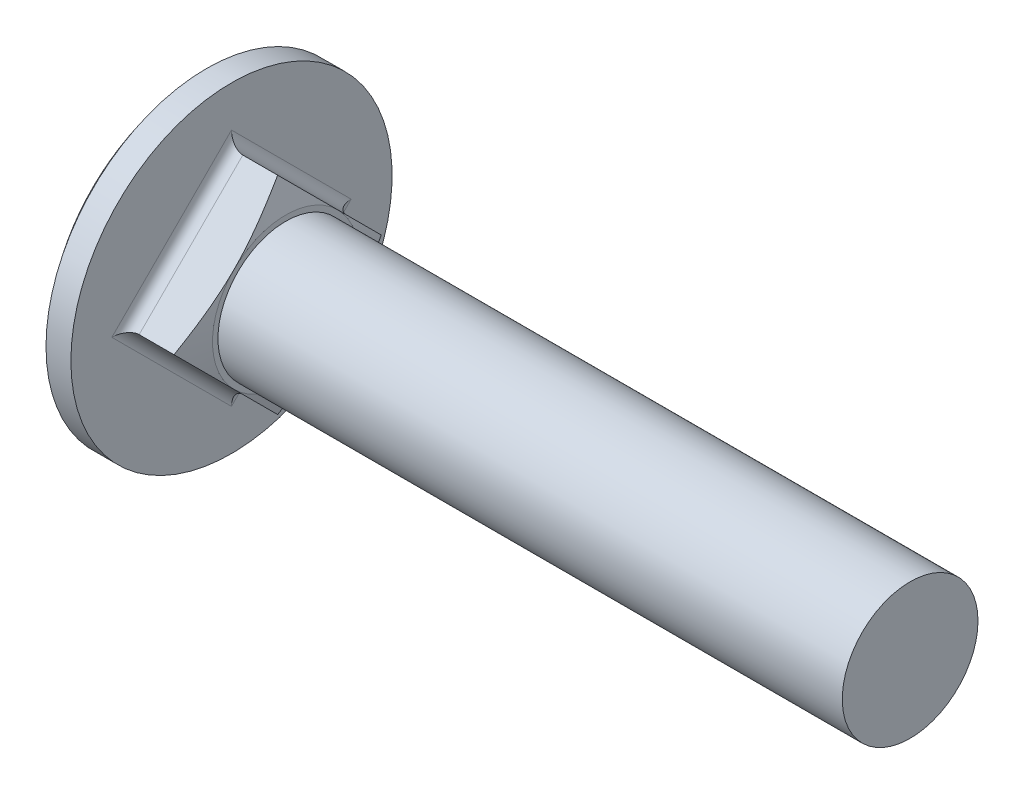
SolidWorks part; units mm, degrees
ref_plane "Front" through (0, 0, 0) normal (0, 0, 1) x (1, 0, 0)
ref_plane "Top" through (0, 0, 0) normal (0, 1, 0) x (1, 0, 0)
ref_plane "Right" through (0, 0, 0) normal (1, 0, 0) x (0, 0, -1)
sketch "Sketch2" plane through (0, 0, 0) normal (0, 0, 1) x (1, 0, 0)
  line L0 (-6.2668, 0) -> (14.9447, 0) construction
  line L1 (3.6, 0) -> (3.6, 7.1)
  line L3 (3.6, 7.1) -> (2.5, 7.1)
  line L4 (0, 0) -> (3.6, 0)
  arc A0 (2.5, 7.1) -> (0, 0) centre (11.332, 0) ccw
  dimension "k" = 3.6
  dimension "c" = 1.1
  dimension "dk" = 14.2
revolve "BaseHead" add sketch "Sketch2" angle 360 about L0
sketch "Sketch3" plane through (3.6, 0, 0) normal (1, 0, 0) x (0, 0, -1)
  line L1 (4.5821, 0) -> (0, 4.5821)
  line L2 (0, 4.5821) -> (-4.5821, 0)
  line L3 (-4.5821, 0) -> (0, -4.5821)
  line L4 (0, -4.5821) -> (4.5821, 0)
  circle A1 centre (0, 0) radius 3.24 construction
extrude "Neck" add sketch "Sketch3" along normal blind 2.4
sketch "Sketch4" plane through (0, 0, 0) normal (0, 0, 1) x (1, 0, 0)
  line L0 (2.9848, 0) -> (9.124, 0) construction
  line L2 (6, 4.5821) -> (6, 3.24)
  line L4 (6, 3.24) -> (5.6404, 4.5821)
  line L6 (5.6404, 4.5821) -> (6, 4.5821)
  line L7 (-6.2668, 0) -> (14.9447, 0) construction
  dimension "D1" = 15
  dimension "D2" = 6.48
revolve "Cut-Extrude1" cut sketch "Sketch4" angle 360 about L0
sketch "Sketch5" plane through (3.6, 0, 0) normal (1, 0, 0) x (0, 0, -1)
  circle A0 centre (0, 0) radius 3
extrude "BaseBody" add sketch "Sketch5" along normal blind 30
cosmetic thread "ThreadCosmetic1" [suppressed] parameters "b"=18, "dn"=5
fillet "Fillet1" radius 0.5 4 edges at (3.6, 2.291, -2.291) (3.6, -2.291, -2.291) (3.6, -2.291, 2.291) (3.6, 2.291, 2.291)
sketch "Sketch7" plane through (0, 0, 0) normal (0, 0, 1) x (1, 0, 0)
  line L0 (33.35, 3.2) -> (33.85, 3.2)
  line L1 (33.85, 3.2) -> (33.85, 3)
  line L2 (33.85, 3) -> (33.6, 2.567)
  line L3 (33.35, 3) -> (33.6, 2.567)
  line L4 (33.35, 3.2) -> (33.35, 3)
  line L5 (35.9661, 0) -> (0, 0) construction
  line L6 (33.35, 3) -> (33.85, 3) construction
  line L7 (33.6, 3) -> (33.6, 2.567) construction
  line L8 (33.6, -3) -> (33.6, 3) construction
  line L10 (33.6, 3) -> (6, 3) construction
  point P5 (33.6, 3.2)
  dimension "D1" = 0.2
  dimension "D2" = 0.5
revolve "Cut-Revolve10" [suppressed] cut sketch "Sketch7" angle 360 about L5
pattern_linear "LPattern10" [suppressed] count 30 spacing 0.6 along (-1, 0, 0) of bodies 106
equation "\"D2@Sketch4\" = \"V@Sketch3\""
equation "\"D2@Sketch7\" =( \"d@Sketch5\" - \"dn@ThreadCosmetic1\") / 2"
equation "\"D3@LPattern10\" = \"D2@Sketch7\" * 1.2"
equation "\"D1@LPattern10\" = \"b@ThreadCosmetic1\" / \"D3@LPattern10\""
